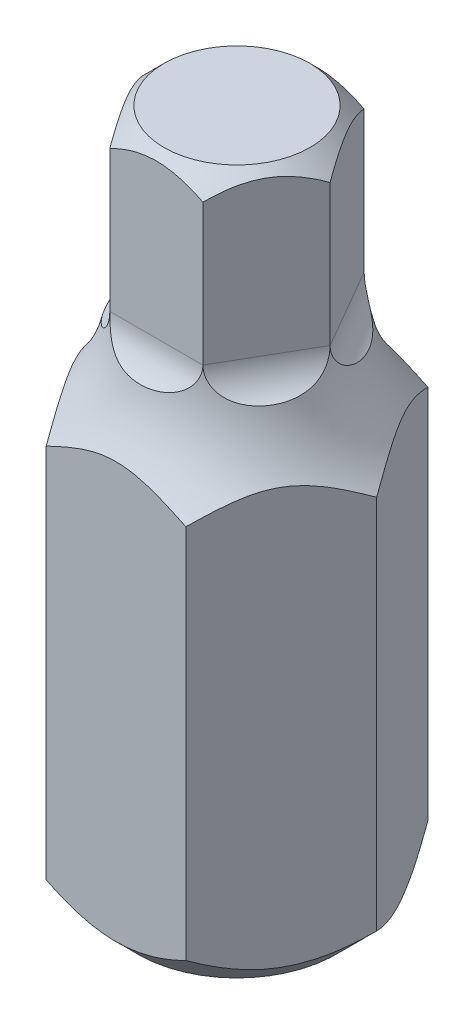
SolidWorks part; units mm, degrees
ref_plane "Front Plane" through (0, 0, 0) normal (0, 0, 1) x (1, 0, 0)
ref_plane "Top Plane" through (0, 0, 0) normal (0, 1, 0) x (1, 0, 0)
ref_plane "Right Plane" through (0, 0, 0) normal (1, 0, 0) x (0, 0, -1)
sketch "Sketch1" plane through (0, 0, 0) normal (0, 1, 0) x (1, 0, 0)
  line L0 (0, 0) -> (0, -3) construction
  line L1 (3.4641, 0) -> (1.7321, 3)
  line L2 (1.7321, 3) -> (-1.7321, 3)
  line L3 (-1.7321, 3) -> (-3.4641, 0)
  line L4 (-3.4641, 0) -> (-1.7321, -3)
  line L5 (-1.7321, -3) -> (1.7321, -3)
  line L6 (1.7321, -3) -> (3.4641, 0)
  circle A0 centre (0, 0) radius 3 construction
  dimension "D1" = 6
extrude "Boss-Extrude1" add sketch "Sketch1" against normal blind 17
sketch "Sketch2" plane through (0, 0, 0) normal (0, 1, 0) x (1, 0, 0)
  line L0 (1.7321, 3) -> (-1.7321, 3) construction
  line L1 (1.1547, -2) -> (2.3094, 0)
  line L2 (2.3094, 0) -> (1.1547, 2)
  line L3 (1.1547, 2) -> (-1.1547, 2)
  line L4 (-1.1547, 2) -> (-2.3094, 0)
  line L5 (-2.3094, 0) -> (-1.1547, -2)
  line L6 (-1.1547, -2) -> (1.1547, -2)
  circle A0 centre (0, 0) radius 2 construction
  point P1 (0, 0)
  dimension "D1" = 4
extrude "Cut-Extrude1" cut sketch "Sketch2" against normal blind 5 flip side to cut
fillet "Fillet4" radius 1 6 edges at (-1.7321, -5, -1) (0, -5, -2) (1.7321, -5, -1) (1.7321, -5, 1) (0, -5, 2) (-1.7321, -5, 1)
sketch "Sketch5" plane through (0, 0, 0) normal (0, 0, 1) x (1, 0, 0)
  line L0 (6.0026, -4) -> (0, -4) construction
  line L1 (-1.1547, -4) -> (1.1547, -4) construction
  line L2 (0, -4) -> (0, -8.8095) construction
  circle A0 centre (6.0026, -4) radius 3.6932
revolve "Cut-Revolve3" cut sketch "Sketch5" angle 360 about L2
sketch "Sketch7" plane through (0, 0, 0) normal (0, 0, 1) x (1, 0, 0)
  line L0 (-1.8094, 0) -> (-3.5871, -1.7777)
  line L4 (-1.8094, 2.6696) -> (-1.8094, 0)
  line L6 (-3.4641, -17) -> (-1.7321, -17) construction
  line L7 (-2.4641, -17) -> (-2.4641, -21.9862)
  line L11 (-1.8094, 2.6696) -> (-3.5871, -1.7777)
  line L12 (-8.9542, -10.5099) -> (-2.4641, -21.9862)
  line L13 (-8.9542, -10.5099) -> (-2.4641, -17)
  line L14 (-2.3094, 0) -> (-1.1547, 0) construction
  line L15 (0, 0) -> (0, -17) construction
  line L16 (-1.7321, -17) -> (1.7321, -17) construction
  dimension "D1" = 45
  dimension "D2" = 45
  dimension "D3" = 0.5
  dimension "D5" = 1
revolve "Cut-Revolve4" cut sketch "Sketch7" angle 360 about L15
